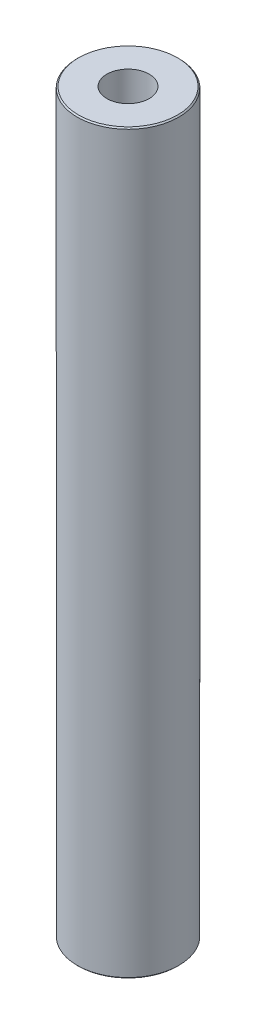
SolidWorks part; units mm, degrees
ref_plane "Front Plane" through (0, 0, 0) normal (0, 0, 1) x (1, 0, 0)
ref_plane "Top Plane" through (0, 0, 0) normal (0, 1, 0) x (1, 0, 0)
ref_plane "Right Plane" through (0, 0, 0) normal (1, 0, 0) x (0, 0, -1)
sketch "Sketch1" plane through (0, 0, 0) normal (0, 1, 0) x (1, 0, 0)
  circle A0 centre (0, 0) radius 32.5
  dimension "SHAFT_OD" = 65
extrude "Boss-Extrude1" add sketch "Sketch1" along normal blind 471.6943
sketch "Sketch2" plane through (0, 0, 0) normal (0, 1, 0) x (1, 0, 0)
  circle A0 centre (0, 0) radius 13.5626
  dimension "BORE_D" = 27.1252
extrude "Cut-Extrude1" cut sketch "Sketch2" along normal through all
chamfer "Chamfer1" distance 0.8013 angle 45 2 edges at (0, 471.6943, 32.5) (0, 0, 32.5)
